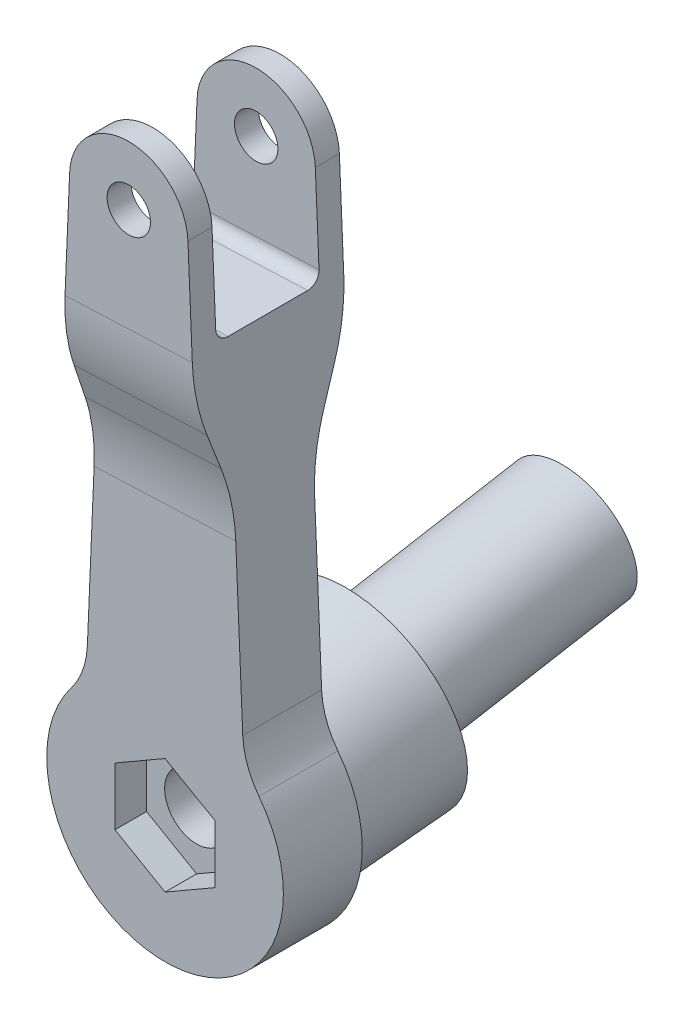
SolidWorks part; units mm, degrees
ref_plane "Front Plane" through (0, 0, 0) normal (0, 0, 1) x (1, 0, 0)
ref_plane "Top Plane" through (0, 0, 0) normal (0, 1, 0) x (1, 0, 0)
ref_plane "Right Plane" through (0, 0, 0) normal (1, 0, 0) x (0, 0, -1)
sketch "Sketch1" plane through (0, 0, 0) normal (0, 0, 1) x (1, 0, 0)
  line L0 (0, 0) -> (0, 69.866) construction
  line L1 (-7.5, 70.1838) -> (-10, 11.1803)
  line L3 (7.5, 70.1838) -> (10, 11.1803)
  arc A6 (-10, 11.1803) -> (10, 11.1803) centre (0, 0) ccw
  circle A7 centre (0, 69.866) radius 2.75
  arc A8 (-7.5, 70.1838) -> (7.5, 70.1838) centre (0, 69.866) cw
  dimension "D1" = 69.866
  dimension "D3" = 30
  dimension "D4" = 5.5
  dimension "D5" = 20
  dimension "D6" = 15
extrude "Boss-Extrude1" add sketch "Sketch1" along normal blind 19.2
sketch "Sketch13" plane through (10.4549, 0.443, 0) normal (0.9991, 0.0423, 0) x (0, 0, -1)
  line L0 (0, 77.3101) -> (-19.2, 77.3101) construction
  line L2 (-16.15, 77.3101) -> (-16.15, 57.3101)
  line L3 (-16.15, 57.3101) -> (-3.05, 57.3101)
  line L4 (-3.05, 77.3101) -> (-3.05, 57.3101)
  line L5 (-16.15, 77.3101) -> (-3.05, 57.3101) construction
  line L6 (-16.15, 57.3101) -> (-3.05, 77.3101) construction
  line L7 (-19.2, 77.3101) -> (-16.15, 77.3101) construction
  line L8 (-19.2, 10.747) -> (-19.2, 69.8034) construction
  line L9 (0, 10.747) -> (0, 69.8034) construction
  line L10 (-19.2, 52.3101) -> (-14.6, 39.6717)
  line L11 (-19.2, 10.747) -> (-19.2, 69.8034) construction
  line L12 (-14.6, 39.6717) -> (-14.6, -15)
  line L13 (-19.2, -15) -> (0, -15) construction
  line L14 (-19.2, 52.3101) -> (-19.2, 77.3101)
  line L15 (-19.2, 77.3101) -> (-16.15, 77.3101)
  line L16 (-9.6, 65.3081) -> (-9.6, -49934.6919) construction
  line L17 (0, 77.3101) -> (-3.05, 77.3101)
  line L18 (0, 52.3101) -> (0, 77.3101)
  line L19 (0, 52.3101) -> (-4.6, 39.6717)
  line L20 (-4.6, 39.6717) -> (-4.6, -15)
  line L21 (-3.05, 77.3101) -> (0, 77.3101) construction
  line L22 (-14.6, -15) -> (-4.6, -15)
  point P4 (-9.6, 67.3101)
  dimension "D1" = 3.05
  dimension "D2" = 20
  dimension "D3" = 160
  dimension "D4" = 5
  dimension "D5" = 10
extrude "Cut-Extrude4" cut sketch "Sketch13" against normal through all both and the other way through all flip side to cut
sketch "Sketch3" plane through (0, 0, 14.6) normal (0, 0, 1) x (1, 0, 0)
  line L1 (0, 7.3323) -> (-6.35, 3.6662)
  line L2 (-6.35, 3.6662) -> (-6.35, -3.6662)
  line L3 (-6.35, -3.6662) -> (0, -7.3323)
  line L4 (0, -7.3323) -> (6.35, -3.6662)
  line L5 (6.35, -3.6662) -> (6.35, 3.6662)
  line L6 (6.35, 3.6662) -> (0, 7.3323)
  circle A0 centre (0, 0) radius 6.35 construction
  dimension "D1" = 12.7
extrude "Cut-Extrude2" cut sketch "Sketch3" against normal blind 4
sketch "Sketch5" plane through (0, 0, 0) normal (1, 0, 0) x (0, 0, -1)
  line L0 (-5, 0) -> (10.4, 2.7154) construction
  line L1 (0, 52.7062) -> (0, 70.1838) construction
  line L2 (-4.6, 40.0791) -> (-4.6, 11.1803) construction
  line L3 (0, 52.7062) -> (0, 70.1838) construction
  point P13 (10.4, 2.7154)
  dimension "D1" = 10
  dimension "D2" = 5
  dimension "D3" = 15
ref_plane "Plane3" through (0, 2.7154, -10.4) normal (0, 0.1736, -0.9848) x (-1, 0, 0)
sketch "Sketch9" plane through (0, 2.7154, -10.4) normal (0, 0.1736, -0.9848) x (-1, 0, 0)
  circle A0 centre (0, -0.8682) radius 13
  circle A2 centre (0, -0.8682) radius 11 construction
  dimension "D1" = 22
  dimension "D2" = 2
sketch "Sketch4" plane through (0, 0, 10.6) normal (0, 0, 1) x (1, 0, 0)
  circle A0 centre (0, 0) radius 4.05
  dimension "D1" = 8.1
extrude "Cut-Extrude3" cut sketch "Sketch4" against normal blind 20
fillet "Fillet4" radius 10 2 edges at (-10, 11.1803, 9.6) (10, 11.1803, 9.6)
extrude "Boss-Extrude2" add sketch "Sketch9" against normal up to surface (13.0922 mm away) up to face at (0, 4.05, 4.6)
sketch "Sketch10" plane through (0, 1.8604, -10.5508) normal (0, 0.1736, -0.9848) x (-1, 0, 0)
  circle A0 centre (0, 0) radius 8
  dimension "D1" = 16
extrude "Boss-Extrude3" add sketch "Sketch10" along normal blind 27
draft "Draft1" type of draft neutral plane draft angle 3 faces to draft 1 face at (0, 12.3894, 4.6) neutral plane through (0, 1.8604, -10.5508) neutral plane normal (0, 0.1736, -0.9848) reverse direction yes parameters "D1"=3
fillet "Fillet5" radius 25 4 edges at (-0.0148, 52.3564, 0) (-0.0158, 39.7066, 4.6) (-0.0158, 39.7066, 14.6) (-0.0148, 52.3564, 19.2)
sketch "Sketch14" plane through (0, 6.5489, -37.1406) normal (0, 0.1736, -0.9848) x (-1, 0, 0)
  line L0 (0, 0) -> (0, -8) construction
  circle A0 centre (-3.4641, 2) radius 2
  circle A1 centre (3.4641, 2) radius 2
  circle A2 centre (0, -4) radius 2
  circle A4 centre (0, 0) radius 8
  circle A5 centre (0, 0) radius 8 construction
  point P9 (0, 0)
  point P10 (0, -4)
  dimension "D1" = 4
  dimension "D2" = 0
  dimension "D4" = 3
extrude "Cut-Extrude5" cut sketch "Sketch14" against normal blind 4
fillet "Fillet6" radius 1.5 3 edges at (0, 11.6862, 4.6) (-0.0144, 57.3609, 3.05) (-0.0144, 57.3609, 16.15)
equation "\"Leg_Tilt\"=10"
equation "\"D1@Sketch5\"=\"Leg_Tilt\""
